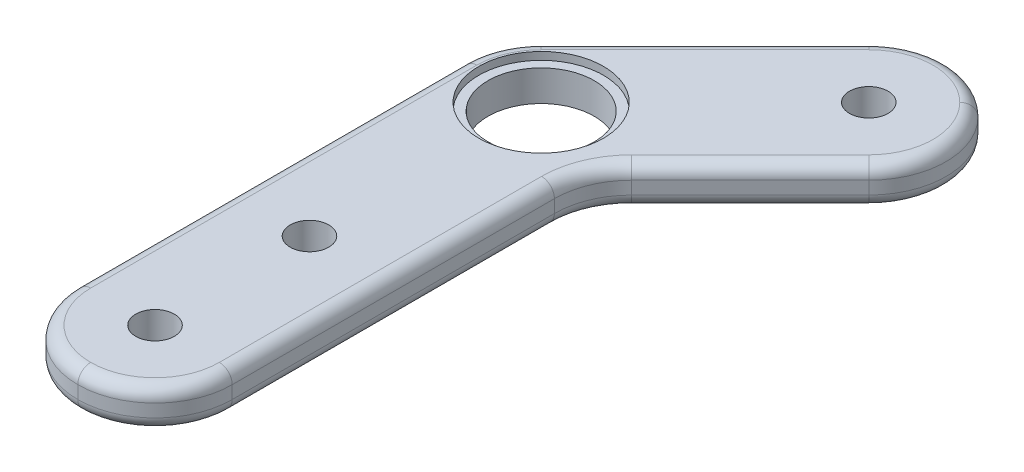
SolidWorks part; units mm, degrees
material "6061 Alloy"
ref_plane "Front Plane" through (0, 0, 0) normal (0, 0, 1) x (1, 0, 0)
ref_plane "Top Plane" through (0, 0, 0) normal (0, 1, 0) x (1, 0, 0)
ref_plane "Right Plane" through (0, 0, 0) normal (1, 0, 0) x (0, 0, -1)
sketch "Sketch1" plane through (0, 0, 0) normal (0, 1, 0) x (1, 0, 0)
  line L0 (0, 44.45) -> (0, -44.45) construction
  line L1 (-12.7, -44.45) -> (12.7, -44.45)
  line L2 (-12.7, -44.45) -> (-12.7, 31.75)
  line L3 (-12.7, 44.45) -> (12.7, 44.45) construction
  line L4 (12.7, -44.45) -> (12.7, 31.75)
  line L5 (-12.7, -44.45) -> (12.7, 44.45) construction
  line L6 (-12.7, 44.45) -> (12.7, -44.45) construction
  line L7 (0, 31.75) -> (35.921, 67.671) construction
  line L8 (8.9803, 22.7697) -> (44.9013, 58.6908)
  line L9 (44.9013, 58.6908) -> (26.9408, 76.6513)
  line L10 (26.9408, 76.6513) -> (-8.9803, 40.7303)
  line L11 (-8.9803, 40.7303) -> (8.9803, 22.7697) construction
  line L12 (12.7, 44.45) -> (12.7, 31.75) construction
  circle A0 centre (0, 31.75) radius 12.7
  circle A1 centre (0, -31.75) radius 3.175
  circle A2 centre (0, -6.35) radius 3.175
  circle A3 centre (0, 31.75) radius 8.7312
  circle A4 centre (26.9408, 58.6908) radius 3.175
  point P0 (0, 0)
  point P16 (35.921, 67.671)
  point P21 (0, 31.75)
  dimension "D4" = 12.7
  dimension "D1" = 6.35
  dimension "D7" = 38.1
  dimension "D8" = 12.7
  dimension "D9" = 17.4625
  dimension "D2" = 25.4
  dimension "D3" = 45
  dimension "D5" = 25.4
  dimension "D6" = 38.1
extrude "Boss-Extrude1" add sketch "Sketch1" along normal blind 6.35 contours A0 L2 L1 L4 L8 A2 A1 | A0 A3 | A0 L4 L8 L9 L10 A4 | A0 L8 L4 region at (-0.0256, 0, 11.0536) region at (-11.4014, 0, -36.4726) region at (11.9359, 0, -26.806) region at (21.2757, 0, -53.0842)
fillet "Fillet2" radius 12.7 5 edges at (12.7, 3.175, -26.4895) (26.9408, 3.175, -76.6513) (44.9013, 3.175, -58.6908) (-12.7, 3.175, 44.45) (12.7, 3.175, 44.45)
fillet "Fillet3" radius 2.1167 20 edges at (13.6667, 0, -26.0891) (12.7, 0, 5.2605) (8.9803, 0, 40.7303) (-8.9803, 0, 40.7303) (-12.7, 0, 0) (-11.7333, 0, -36.6101) (4.4901, 0, -54.2006) (26.9408, 0, -71.3908) (39.6408, 0, -58.6908) (13.6667, 6.35, -26.0891) (12.7, 6.35, 5.2605) (8.9803, 6.35, 40.7303) (-8.9803, 6.35, 40.7303) (-12.7, 6.35, 0) (-11.7333, 6.35, -36.6101) (4.4901, 6.35, -54.2006) (26.9408, 6.35, -71.3908) (39.6408, 6.35, -58.6908) (26.1704, 0, -39.9599) (26.1704, 6.35, -39.9599)
sketch "Sketch2" plane through (0, 6.35, 0) normal (0, 1, 0) x (1, 0, 0)
  circle A0 centre (0, 31.75) radius 10.2489
  dimension "D1" = 20.4978
extrude "Cut-Extrude1" cut sketch "Sketch2" against normal blind 1.27
